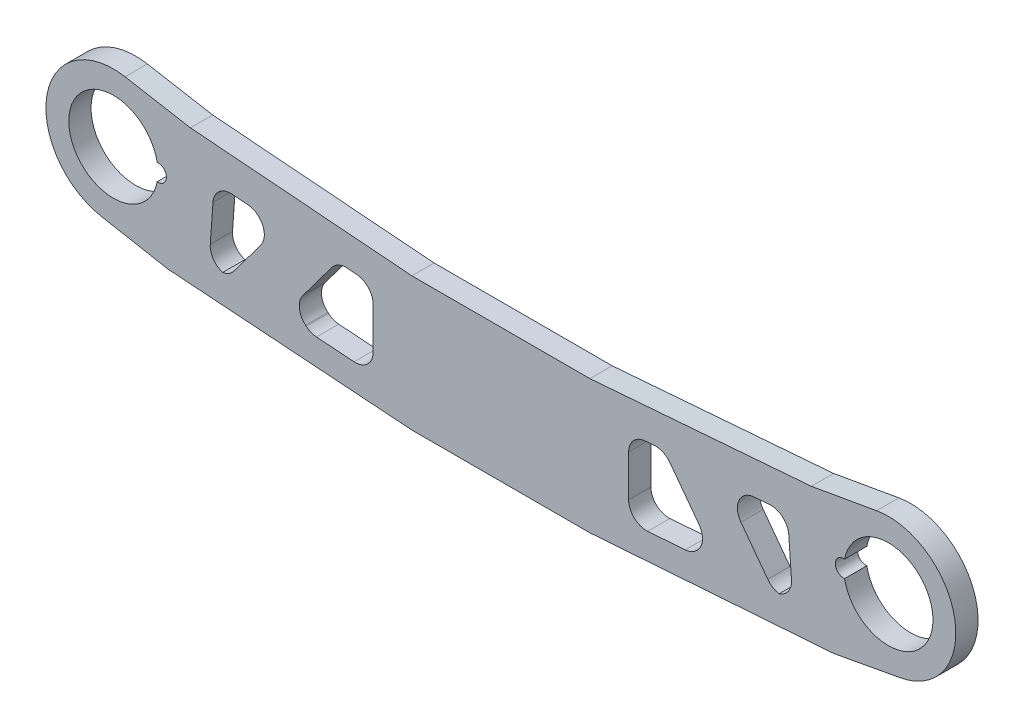
SolidWorks part; units mm, degrees
ref_plane "Ön Düzlem" through (0, 0, 0) normal (0, 0, 1) x (1, 0, 0)
ref_plane "Üst Düzlem" through (0, 0, 0) normal (0, 1, 0) x (1, 0, 0)
ref_plane "Sağ Düzlem" through (0, 0, 0) normal (1, 0, 0) x (0, 0, -1)
sketch "Çizim1" plane through (0, 0, 0) normal (0, 0, 1) x (1, 0, 0)
  line L1 (0, 14.7648) -> (20, 14.7648)
  line L2 (0, -15.2354) -> (20, -15.2354)
  line L3 (0, 0) -> (0, 14.7648)
  line L6 (69.7302, 18.6869) -> (84.4093, 21.2752)
  line L7 (0, 0) -> (0, -15.2354)
  line L10 (74.8288, -11.3134) -> (89.5787, -8.5859)
  line L11 (20, 14.7648) -> (69.7302, 18.6869)
  line L12 (20, -15.2354) -> (74.8288, -11.3134)
  arc A4 (84.4093, 21.2752) -> (89.5787, -8.5859) centre (87.0405, 6.3527) cw
  dimension "D2" = 54.9689
  dimension "D1" = 15
extrude "Yükseklik-Ekstrüzyon3" add sketch "Çizim1" along normal blind 5 contours L7 L2 L12 L10 A4 L6 L11 L1 L3
sketch "Çizim2" plane through (0, 0, 0) normal (0, 0, 1) x (1, 0, 0)
  line L0 (28.6959, -8.7523) -> (42.7317, -7.7483)
  line L2 (28.6959, 8.5533) -> (28.6959, -8.7523)
  line L13 (49.5831, 9.5986) -> (61.257, -6.0359)
  line L15 (61.257, -6.0359) -> (65.5653, -5.7278)
  line L16 (65.5653, -5.7278) -> (64.376, 10.7652)
  line L17 (64.376, 10.7652) -> (49.5831, 9.5986)
  line L19 (36.6505, 9.1806) -> (28.6959, 8.5533)
  line L20 (42.7317, -7.7483) -> (46.7353, -4.3257)
  line L21 (46.7353, -4.3257) -> (36.6505, 9.1806)
  line L25 (20, -15.2354) -> (74.8288, -11.3134) construction
  line L26 (20, 14.7648) -> (69.7302, 18.6869) construction
  arc A0 (77.201, 4.4648) -> (77.201, 8.2405) centre (87.0405, 6.3527) ccw
  arc A1 (77.201, 8.2405) -> (77.201, 4.4648) centre (77.0216, 6.3527) ccw
  point P7 (48.5287, 10.9692)
  point P9 (58.3072, -1.7419)
  point P10 (49.86, -7.9205)
  point P11 (43.8926, -4.8197)
  point P12 (38.6274, -7.9672)
  point P13 (36.6613, 9.0244)
  point P14 (42.4477, -9.0752)
  point P16 (49.86, -8.3245)
  point P18 (45.4581, -3.7127)
  point P19 (67.4803, -4.2304)
  point P20 (36.9326, -6.3653)
  point P24 (54.2677, -4.7926)
  point P25 (31.9497, 8.6548)
  point P26 (47.4314, -4.8197)
  point P28 (46.7117, -4.2304)
  point P29 (42.4477, -2.0444)
  point P30 (49.86, -1.3045)
  point P31 (0, 0)
  point P32 (48.5598, -1.4102)
  point P33 (0, 0)
  point P34 (48.5598, -4.7926)
  point P35 (42.7262, -7.6742)
  point P36 (43.2747, -4.7926)
  point P37 (48.1928, -4.5291)
  point P38 (42.1605, -1.9485)
  point P39 (45.3029, -0.3161)
  point P40 (44.1046, 1.5474)
  point P41 (48.1928, 2.7301)
  point P42 (39.9217, 9.3215)
  point P43 (43.6491, 3.6039)
  point P44 (47.0023, 4.4648)
  point P45 (45.3029, 7.537)
  point P46 (44.8639, 7.6907)
  point P47 (43.2747, 4.4648)
  point P48 (41.4516, -6.3653)
  point P49 (39.5222, -6.7263)
  point P50 (51.6451, -5.0021)
  point P51 (43.6007, -0.3453)
  point P52 (47.0573, 4.8785)
  point P53 (45.331, 4.4648)
  point P54 (29.6652, 8.2304)
  point P55 (58.9998, 11.4073)
  point P56 (62.889, -4.7452)
  point P57 (67.4542, -4.5791)
  dimension "D1" = 19.512
extrude "Kes-Ekstrüzyon3" cut sketch "Çizim2" along normal blind 16
fillet "Radyus1" radius 4 9 edges at (28.6959, -8.7523, 2.5) (64.376, 10.7652, 2.5) (49.5831, 9.5986, 2.5) (65.5653, -5.7278, 2.5) (46.7353, -4.3257, 2.5) (36.6505, 9.1806, 2.5) (28.6959, 8.5533, 2.5) (42.7317, -7.7483, 2.5) (61.257, -6.0359, 2.5)
mirror "Aynalama1" about plane through (0, 0, 5) normal (1, 0, 0) of "Kes-Ekstrüzyon3", "Yükseklik-Ekstrüzyon3", "Radyus1"
